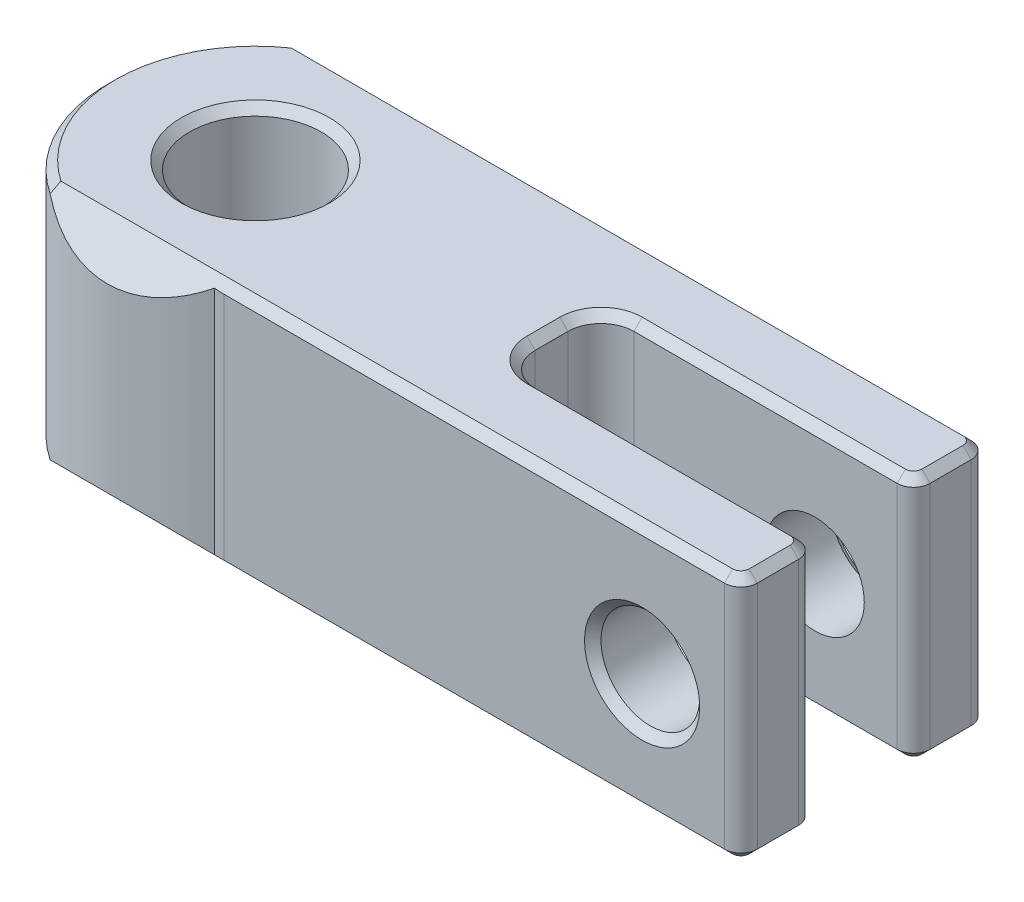
SolidWorks part; units mm, degrees
material "PLA"
ref_plane "Front Plane" through (0, 0, 0) normal (0, 0, 1) x (1, 0, 0)
ref_plane "Top Plane" through (0, 0, 0) normal (0, 1, 0) x (1, 0, 0)
ref_plane "Right Plane" through (0, 0, 0) normal (1, 0, 0) x (0, 0, -1)
sketch "Sketch1" plane through (0, 0, 0) normal (0, 1, 0) x (1, 0, 0)
  circle A0 centre (0, 0) radius 9
  circle A1 centre (0, 0) radius 4
  dimension "D1" = 8
  dimension "D2" = 18
extrude "Boss-Extrude1" add sketch "Sketch1" along normal mid plane 15
sketch "Sketch2" plane through (0, 0, 0) normal (0, 1, 0) x (1, 0, 0)
  line L0 (0, 0) -> (4, 0) construction
  line L1 (4, 0) -> (5, 0) construction
  line L2 (5, 0) -> (37, 0) construction
  line L4 (5, -7.5) -> (37, -7.5)
  line L5 (5, -7.5) -> (5, 7.5)
  line L6 (5, 7.5) -> (37, 7.5)
  line L7 (37, -7.5) -> (37, 7.5)
  circle A0 centre (0, 0) radius 4 construction
  point P12 (5, 0)
  dimension "D1" = 5
  dimension "D2" = 32
  dimension "D3" = 15
extrude "Boss-Extrude2" add sketch "Sketch2" along normal mid plane 15
sketch "Sketch3" plane through (0, 0, 0) normal (0, 1, 0) x (1, 0, 0)
  line L0 (37, -7.5) -> (37, 7.5) construction
  line L1 (18, -3) -> (56, -3)
  line L2 (18, -3) -> (18, 3)
  line L3 (18, 3) -> (56, 3)
  line L4 (56, -3) -> (56, 3)
  line L5 (18, -3) -> (56, 3) construction
  line L6 (18, 3) -> (56, -3) construction
  point P0 (37, 0)
  dimension "D1" = 6
  dimension "D2" = 38
extrude "Cut-Extrude1" cut sketch "Sketch3" against normal mid plane 38
sketch "Sketch4" plane through (0, 0, -3) normal (0, 0, 1) x (1, 0, 0)
  line L0 (37, -0.2671) -> (25, -0.2671) construction
  line L1 (37, 7.5) -> (37, -7.5) construction
  circle A0 centre (31, -0.2671) radius 3
  dimension "D2" = 6
  dimension "D1" = 12
extrude "Cut-Extrude2" cut sketch "Sketch4" against normal mid plane 44
fillet "Fillet1" radius 2 2 edges at (18, 0, 3) (18, 0, -3)
fillet "Fillet2" radius 1 4 edges at (37, 0, -7.5) (37, 0, -3) (37, 0, 3) (37, 0, 7.5)
chamfer "Chamfer1" distance 0.5 angle 45 4 edges at (0, -7.5, 4) (0, 7.5, 4) (34, -0.2671, -7.5) (28, -0.2671, 7.5)
chamfer "Chamfer2" distance 0.5 angle 45 26 edges at (20.5, -7.5, -7.5) (36.7071, -7.5, -7.2071) (37, -7.5, -5.25) (36.7071, -7.5, -3.2929) (28, -7.5, -3) (18.5858, -7.5, -2.4142) (18, -7.5, 0) (18.5858, -7.5, 2.4142) (28, -7.5, 3) (36.7071, -7.5, 3.2929) (37, -7.5, 5.25) (36.7071, -7.5, 7.2071) (20.5, -7.5, 7.5) (20.5, 7.5, -7.5) (36.7071, 7.5, -7.2071) (37, 7.5, -5.25) (36.7071, 7.5, -3.2929) (28, 7.5, -3) (18.5858, 7.5, -2.4142) (18, 7.5, 0) (18.5858, 7.5, 2.4142) (28, 7.5, 3) (36.7071, 7.5, 3.2929) (37, 7.5, 5.25) (36.7071, 7.5, 7.2071) (20.5, 7.5, 7.5)
chamfer "Chamfer3" distance 0.5 angle 45 2 edges at (-9, 7.5, 0) (-9, -7.5, 0)
fillet "Fillet3" radius 10 2 edges at (5, 0, -7.5) (5, 0, 7.5)
